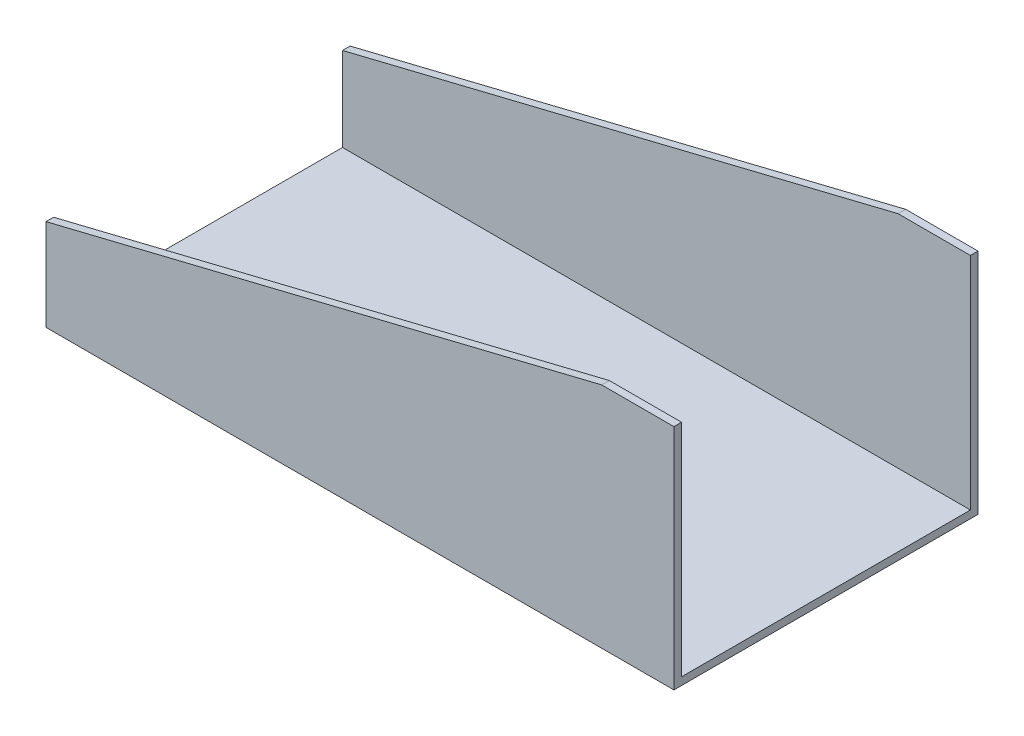
SolidWorks part; units mm, degrees
ref_plane "Front Plane" through (0, 0, 0) normal (0, 0, 1) x (1, 0, 0)
ref_plane "Top Plane" through (0, 0, 0) normal (0, 1, 0) x (1, 0, 0)
ref_plane "Right Plane" through (0, 0, 0) normal (1, 0, 0) x (0, 0, -1)
sketch "Sketch1" plane through (0, 0, 0) normal (0, 1, 0) x (1, 0, 0)
  line L0 (-48.5648, -24.6411) -> (56.3372, -24.6411)
  line L1 (-48.5648, 24.8889) -> (56.3372, 24.8889)
  line L2 (-48.5648, 24.8889) -> (-48.5648, -25.9111)
  line L3 (-48.5648, -25.9111) -> (56.3372, -25.9111)
  line L4 (56.3372, 24.8889) -> (56.3372, -25.9111)
  line L5 (-48.5648, 23.6189) -> (56.3372, 23.6189)
  dimension "D1" = 50.8
  dimension "D2" = 104.902
  dimension "D3" = 1.27
  dimension "D4" = 1.27
extrude "Boss-Extrude1" add sketch "Sketch1" along normal blind 1.27 contours L5 L2 L0 L4 region at (3.8862, 0, 0.5111)
extrude "Boss-Extrude2" add sketch "Sketch1<3>" along normal blind 38.1 contours L4 L0 L2 L3 | L2 L5 L4 L1 region at (3.8862, 0, 25.2761) region at (3.8862, 0, -24.2539)
sketch "Sketch1<3>" plane through (0, 0, 0) normal (0, 1, 0) x (1, 0, 0) same geometry as "Sketch1"
sketch "Sketch2" plane through (0, 0, 25.9111) normal (0, 0, 1) x (1, 0, 0)
  line L0 (-48.5648, 15.3073) -> (44.2625, 38.1)
  line L1 (-48.5648, 38.1) -> (-48.5648, 0) construction
  line L2 (-48.5648, 38.1) -> (56.3372, 38.1) construction
  line L3 (-48.5648, 15.3073) -> (-48.5648, 38.1)
  line L4 (-48.5648, 38.1) -> (44.2625, 38.1)
extrude "Cut-Extrude1" cut sketch "Sketch2" against normal blind 53.34
